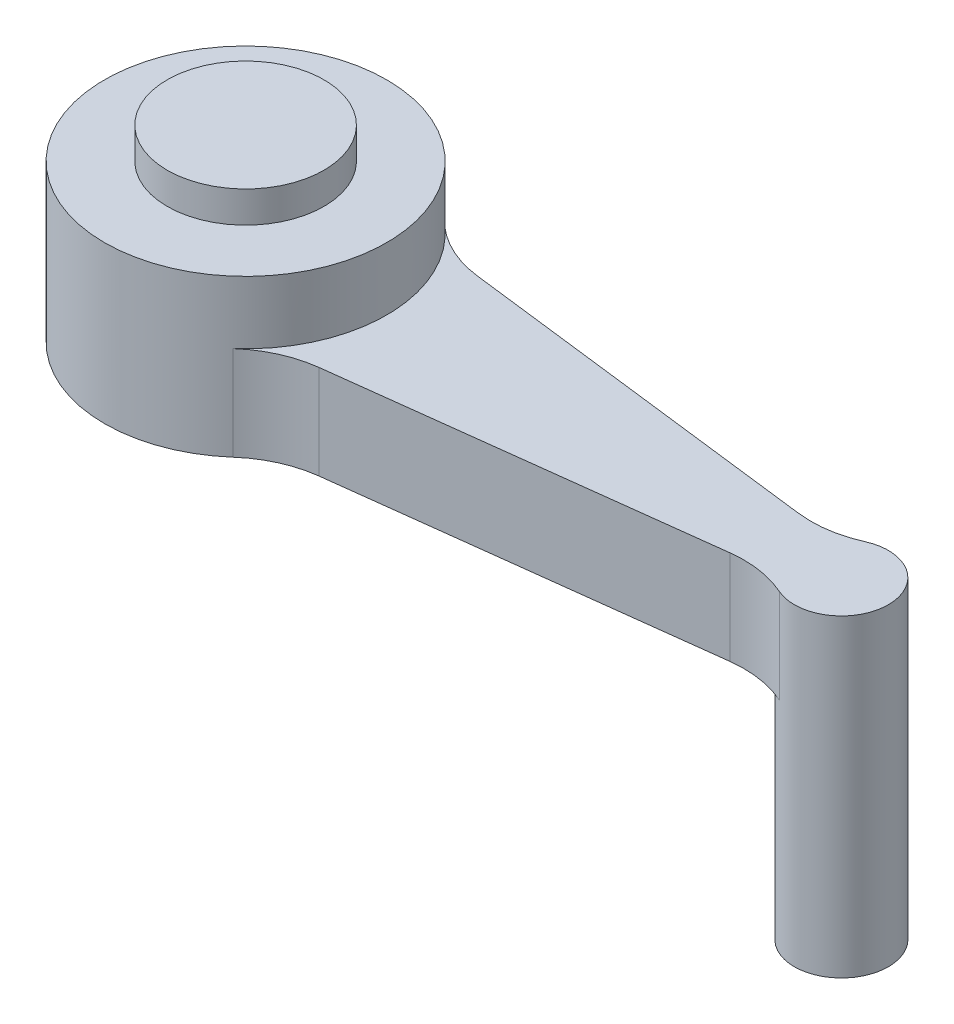
SolidWorks part; units mm, degrees
ref_plane "Front Plane" through (0, 0, 0) normal (0, 0, 1) x (1, 0, 0)
ref_plane "Top Plane" through (0, 0, 0) normal (0, 1, 0) x (1, 0, 0)
ref_plane "Right Plane" through (0, 0, 0) normal (1, 0, 0) x (0, 0, -1)
sketch "Sketch1" plane through (0, 0, 0) normal (0, 1, 0) x (1, 0, 0)
  line L0 (-9.5, 0) -> (9.5, 0) construction
  circle A0 centre (-9.5, 0) radius 4.5
  circle A1 centre (9.5, 0) radius 1.5
  dimension "D2" = 9
  dimension "D3" = 3
  dimension "D1" = 19
extrude "Boss-Extrude1" add sketch "Sketch1" along normal blind 5 contours A0
extrude "Boss-Extrude2" add sketch "Sketch1<3>" along normal blind 3 and the other way blind 7 separate body contours A1
sketch "Sketch1<3>" plane through (0, 0, 0) normal (0, 1, 0) x (1, 0, 0) same geometry as "Sketch1"
sketch "Sketch2" plane through (0, 0, 0) normal (0, 1, 0) x (1, 0, 0)
  line L0 (-14, 0) -> (11, 0) construction
  line L1 (-4.635, 2.5261) -> (7.0376, 1.0929)
  line L2 (-4.635, -2.5261) -> (7.0376, -1.0929)
  circle A0 centre (-9.5, 0) radius 4.5 construction
  circle A1 centre (9.5, 0) radius 1.5 construction
  arc A2 (7.0376, 1.0929) -> (8.8893, 1.37) centre (7.4642, 4.5668) ccw
  arc A3 (8.8893, 1.37) -> (8.8893, -1.37) centre (9.5, 0) ccw
  arc A4 (-6.5235, -3.375) -> (-6.5235, 3.375) centre (-9.5, 0) ccw
  arc A5 (-4.635, 2.5261) -> (-6.5235, 3.375) centre (-4.2085, 6) cw
  arc A6 (7.0376, -1.0929) -> (8.8893, -1.37) centre (7.4642, -4.5668) cw
  arc A7 (-4.635, -2.5261) -> (-6.5235, -3.375) centre (-4.2085, -6) ccw
  point P11 (-6.1719, 3.7618)
  point P12 (9.169, 1.463)
  dimension "D1" = 3.5
  dimension "D3" = 3.5
  dimension "D2" = 6
  dimension "D4" = 7
extrude "Boss-Extrude3" add sketch "Sketch2" along normal blind 3
sketch "Sketch3" plane through (0, 5, 0) normal (0, 1, 0) x (1, 0, 0)
  circle A0 centre (-9.5, 0) radius 2.5
  dimension "D1" = 5
extrude "Boss-Extrude4" add sketch "Sketch3" along normal blind 1
